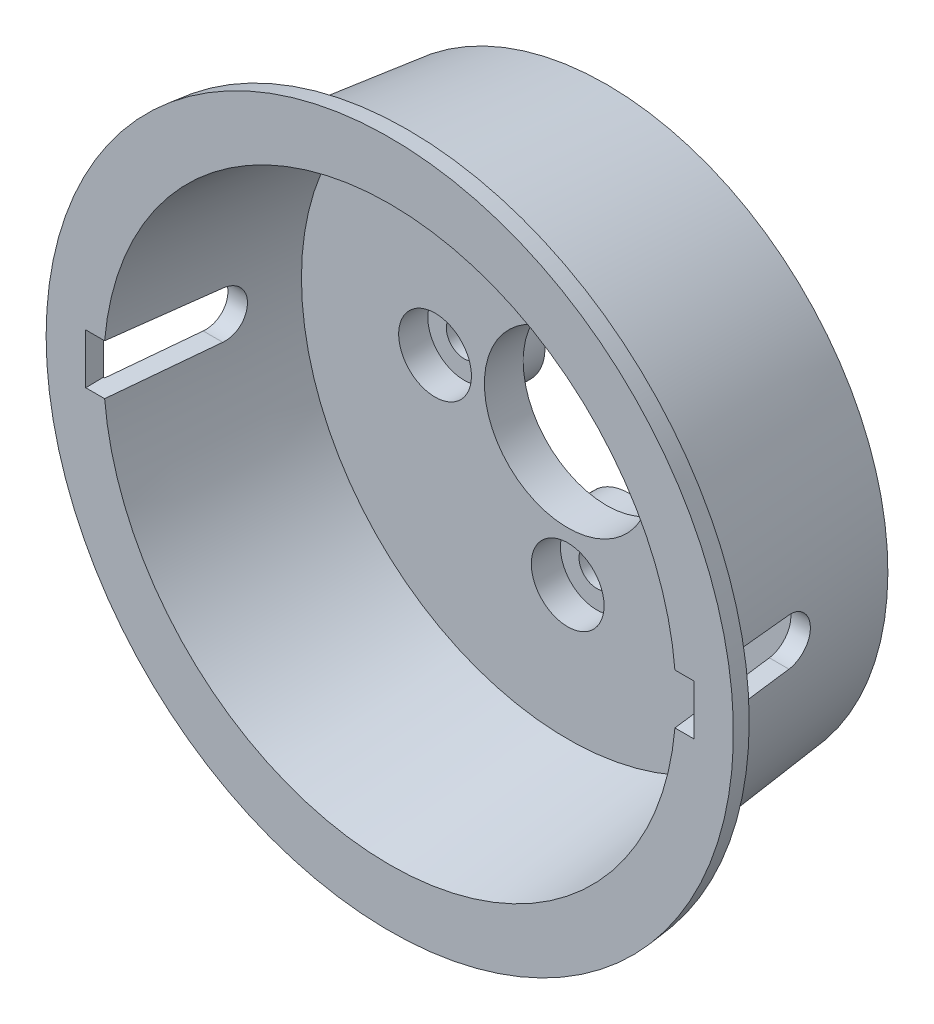
SolidWorks part; units mm, degrees
ref_plane "Plan de face" through (0, 0, 0) normal (0, 0, 1) x (1, 0, 0)
ref_plane "Plan de dessus" through (0, 0, 0) normal (0, 1, 0) x (1, 0, 0)
ref_plane "Plan de droite" through (0, 0, 0) normal (1, 0, 0) x (0, 0, -1)
sketch "Esquisse2" plane through (0, 0, 0) normal (1, 0, 0) x (0, 0, -1)
  line L0 (0, 0) -> (0, 17.4)
  line L1 (0, 17.4) -> (-12.3, 18.7838)
  line L2 (-12.3, 18.7838) -> (-12.3, 21.1262)
  line L3 (-12.3, 21.1262) -> (-13.4, 21.25)
  line L4 (-13.4, 21.25) -> (-13.4, 17.7)
  line L5 (-13.4, 17.7) -> (-2.4, 16.4624)
  line L6 (-2.4, 16.4624) -> (-2.4, 0)
  line L7 (0, 0) -> (-28.0135, 0) construction
  line L8 (0, 0) -> (-2.4, 0)
  dimension "D1" = 21.25
  dimension "D2" = 1.1
  dimension "D3" = 1.2
  dimension "D4" = 13.4
  dimension "D5" = 17.4
  dimension "D6" = 17.7
  dimension "D7" = 11
  dimension "D8" = 2.4
revolve "Révolution1" add sketch "Esquisse2" angle 360 about L7
sketch "Esquisse3" plane through (0, 0, 0) normal (0, 0, -1) x (-1, 0, 0)
  line L0 (0, 0) -> (0, -17.4) construction
  circle A0 centre (0, -8.1999) radius 1.8
  circle A1 centre (0, -8.1999) radius 3
  circle A2 centre (-8.1999, 0) radius 1.8
  circle A3 centre (-8.1999, 0) radius 3
  circle A4 centre (0, 8.1999) radius 1.8
  circle A5 centre (0, 8.1999) radius 3
  circle A6 centre (8.1999, 0) radius 1.8
  circle A7 centre (8.1999, 0) radius 3
  circle A8 centre (0, 0) radius 17.4 construction
  point P16 (0, 0)
  dimension "D2" = 6
  dimension "D3" = 3.6
  dimension "D4" = 8.1999
  dimension "D1" = 4
extrude "Boss.-Extru.1" add sketch "Esquisse3" along normal blind 1.4
sketch "Esquisse6" plane through (0, 0, 2.4) normal (0, 0, 1) x (1, 0, 0)
  circle A0 centre (0, 8.1999) radius 2.25
  circle A1 centre (8.1999, 0) radius 2.25
  circle A2 centre (0, -8.1999) radius 2.25
  circle A3 centre (-8.1999, 0) radius 2.25
  point P12 (0, 0)
  dimension "D2" = 4.5
  dimension "D1" = 4
extrude "Enlèv. mat.-Extru.2" cut sketch "Esquisse6" against normal blind 1.8
sketch "Esquisse4" plane through (0, 0, 2.4) normal (0, 0, 1) x (1, 0, 0)
  circle A0 centre (0, 0) radius 5.15
  circle A1 centre (0, 8.1999) radius 1.1
  circle A2 centre (8.1999, 0) radius 1.1
  circle A3 centre (0, -8.1999) radius 1.1
  circle A4 centre (-8.1999, 0) radius 1.1
  point P15 (0, 0)
  dimension "D1" = 10.3
  dimension "D3" = 2.2
  dimension "D2" = 4
extrude "Enlèv. mat.-Extru.1" cut sketch "Esquisse4" against normal through all
sketch "Esquisse7" plane through (0, 0, 0) normal (1, 0, 0) x (0, 0, -1)
  line L0 (-13.4, 1.55) -> (-6.8279, 1.4498)
  line L1 (0, 0) -> (-13.4, 0) construction
  line L2 (-13.4, 21.25) -> (-13.4, -21.25) construction
  line L3 (-13.4, -1.55) -> (-6.8279, -1.4498)
  line L4 (-13.4, 1.55) -> (-13.4, -1.55)
  arc A0 (-6.8279, 1.4498) -> (-6.8279, -1.4498) centre (-6.85, 0) cw
  dimension "D2" = 1.45
  dimension "D1" = 3.1
  dimension "D3" = 6.55
extrude "Enlèv. mat.-Extru.3" cut sketch "Esquisse7" against normal blind 18.8 and the other way blind 18.8
